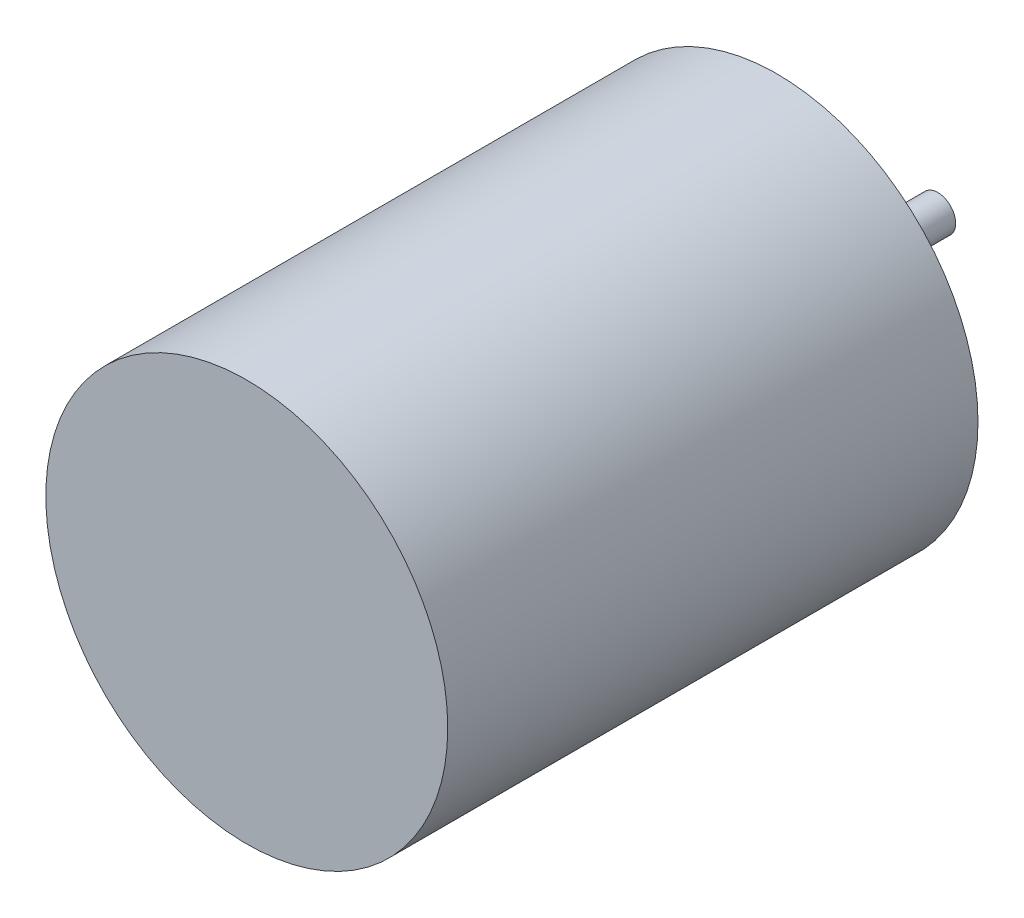
SolidWorks part; units mm, degrees
ref_plane "Front Plane" through (0, 0, 0) normal (0, 0, 1) x (1, 0, 0)
ref_plane "Top Plane" through (0, 0, 0) normal (0, 1, 0) x (1, 0, 0)
ref_plane "Right Plane" through (0, 0, 0) normal (1, 0, 0) x (0, 0, -1)
sketch "Sketch1" plane through (0, 0, 0) normal (0, 0, 1) x (1, 0, 0)
  circle A0 centre (0, 0) radius 71.4375
  dimension "D1" = 142.875
extrude "Boss-Extrude1" add sketch "Sketch1" along normal blind 188.4934
sketch "Sketch2" plane through (0, 0, 0) normal (0, 0, 1) x (1, 0, 0)
  circle A0 centre (0, 0) radius 6.35
  dimension "D1" = 12.7
extrude "Boss-Extrude2" add sketch "Sketch2" against normal blind 57.15
